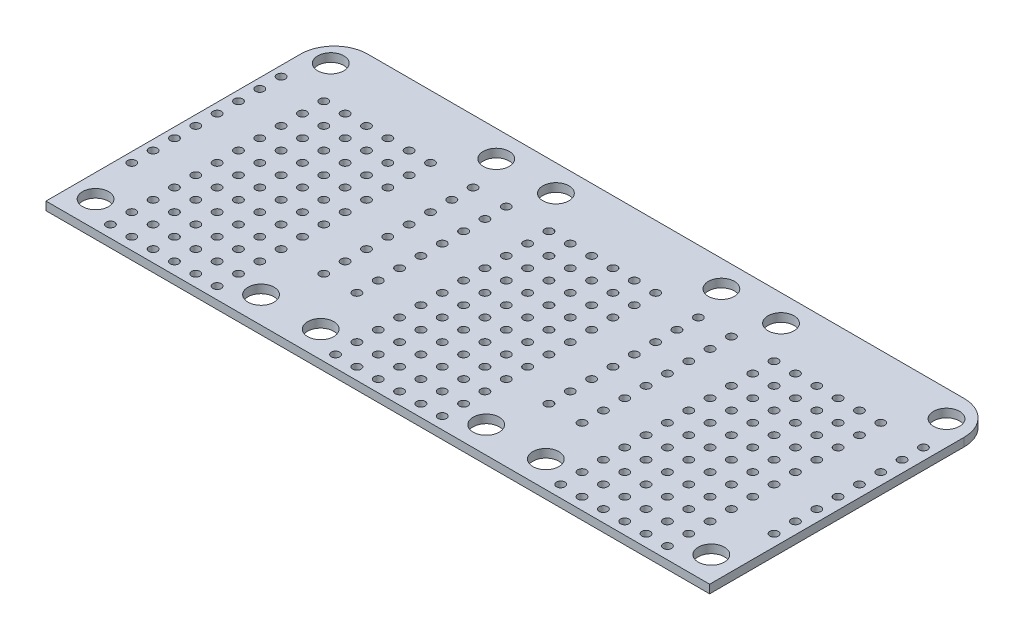
SolidWorks part; units mm, degrees
ref_plane "Front Plane" through (0, 0, 0) normal (0, 0, 1) x (1, 0, 0)
ref_plane "Top Plane" through (0, 0, 0) normal (0, 1, 0) x (1, 0, 0)
ref_plane "Right Plane" through (0, 0, 0) normal (1, 0, 0) x (0, 0, -1)
sketch "board" plane through (0, 0, 0) normal (0, 1, 0) x (1, 0, 0)
  line L1 (0, 0) -> (79, 0)
  line L2 (0, 0) -> (0, 34.3)
  line L3 (0, 34.3) -> (79, 34.3)
  line L4 (79, 0) -> (79, 34.3)
  dimension "D1" = 79
  dimension "D2" = 34.3
sketch "holes" plane through (0, 0, 0) normal (0, 1, 0) x (1, 0, 0)
  line L0 (0, 26.82) -> (1.17, 26.82) construction
  line L5 (1.17, 26.82) -> (6.25, 26.82) construction
  line L6 (2.75, 3.15) -> (22.45, 3.15) construction
  line L7 (22.45, 3.15) -> (22.45, 31.15) construction
  line L8 (22.45, 31.15) -> (2.75, 31.15) construction
  line L9 (2.75, 31.15) -> (2.75, 3.15) construction
  line L10 (12.6, 0) -> (12.6, 3.15) construction
  line L11 (6.25, 26.82) -> (6.25, 24.28) construction
  line L12 (6.25, 26.82) -> (8.79, 26.82) construction
  line L13 (1.17, 26.82) -> (24.03, 26.82) construction
  line L14 (0, 0) -> (2.75, 0) construction
  line L15 (2.75, 0) -> (2.75, 3.15) construction
  line L16 (2.75, 0) -> (12.6, 0) construction
  line L17 (1.17, 26.82) -> (1.17, 24.28) construction
  line L18 (0, 0) -> (0, 26.82) construction
  circle A0 centre (2.75, 31.15) radius 1.55
  circle A1 centre (22.45, 31.15) radius 1.55
  circle A2 centre (22.45, 3.15) radius 1.55
  circle A3 centre (2.75, 3.15) radius 1.55
  circle A4 centre (1.17, 26.82) radius 0.5
  circle A5 centre (24.03, 26.82) radius 0.5
  circle A6 centre (6.25, 26.82) radius 0.5
  circle A12 centre (1.17, 24.28) radius 0.5
  circle A13 centre (24.03, 24.28) radius 0.5
  circle A14 centre (1.17, 21.74) radius 0.5
  circle A15 centre (24.03, 21.74) radius 0.5
  circle A16 centre (1.17, 19.2) radius 0.5
  circle A17 centre (24.03, 19.2) radius 0.5
  circle A18 centre (1.17, 16.66) radius 0.5
  circle A19 centre (24.03, 16.66) radius 0.5
  circle A20 centre (1.17, 14.12) radius 0.5
  circle A21 centre (24.03, 14.12) radius 0.5
  circle A22 centre (1.17, 11.58) radius 0.5
  circle A23 centre (24.03, 11.58) radius 0.5
  circle A24 centre (1.17, 9.04) radius 0.5
  circle A25 centre (24.03, 9.04) radius 0.5
  circle A26 centre (6.25, 24.28) radius 0.5
  circle A27 centre (6.25, 21.74) radius 0.5
  circle A28 centre (6.25, 19.2) radius 0.5
  circle A29 centre (6.25, 16.66) radius 0.5
  circle A30 centre (6.25, 14.12) radius 0.5
  circle A31 centre (6.25, 11.58) radius 0.5
  circle A32 centre (6.25, 9.04) radius 0.5
  circle A33 centre (6.25, 6.5) radius 0.5
  circle A34 centre (6.25, 3.96) radius 0.5
  circle A35 centre (6.25, 1.42) radius 0.5
  circle A36 centre (8.79, 24.28) radius 0.5
  circle A37 centre (8.79, 21.74) radius 0.5
  circle A38 centre (8.79, 19.2) radius 0.5
  circle A39 centre (8.79, 16.66) radius 0.5
  circle A40 centre (8.79, 14.12) radius 0.5
  circle A41 centre (8.79, 11.58) radius 0.5
  circle A42 centre (8.79, 9.04) radius 0.5
  circle A43 centre (8.79, 6.5) radius 0.5
  circle A44 centre (8.79, 3.96) radius 0.5
  circle A45 centre (8.79, 1.42) radius 0.5
  circle A46 centre (11.33, 24.28) radius 0.5
  circle A47 centre (11.33, 21.74) radius 0.5
  circle A48 centre (11.33, 19.2) radius 0.5
  circle A49 centre (11.33, 16.66) radius 0.5
  circle A50 centre (11.33, 14.12) radius 0.5
  circle A51 centre (11.33, 11.58) radius 0.5
  circle A52 centre (11.33, 9.04) radius 0.5
  circle A53 centre (11.33, 6.5) radius 0.5
  circle A54 centre (11.33, 3.96) radius 0.5
  circle A55 centre (11.33, 1.42) radius 0.5
  circle A56 centre (13.87, 24.28) radius 0.5
  circle A57 centre (13.87, 21.74) radius 0.5
  circle A58 centre (13.87, 19.2) radius 0.5
  circle A59 centre (13.87, 16.66) radius 0.5
  circle A60 centre (13.87, 14.12) radius 0.5
  circle A61 centre (13.87, 11.58) radius 0.5
  circle A62 centre (13.87, 9.04) radius 0.5
  circle A63 centre (13.87, 6.5) radius 0.5
  circle A64 centre (13.87, 3.96) radius 0.5
  circle A65 centre (13.87, 1.42) radius 0.5
  circle A66 centre (16.41, 24.28) radius 0.5
  circle A67 centre (16.41, 21.74) radius 0.5
  circle A68 centre (16.41, 19.2) radius 0.5
  circle A69 centre (16.41, 16.66) radius 0.5
  circle A70 centre (16.41, 14.12) radius 0.5
  circle A71 centre (16.41, 11.58) radius 0.5
  circle A72 centre (16.41, 9.04) radius 0.5
  circle A73 centre (16.41, 6.5) radius 0.5
  circle A74 centre (16.41, 3.96) radius 0.5
  circle A75 centre (16.41, 1.42) radius 0.5
  circle A76 centre (18.95, 24.28) radius 0.5
  circle A77 centre (18.95, 21.74) radius 0.5
  circle A78 centre (18.95, 19.2) radius 0.5
  circle A79 centre (18.95, 16.66) radius 0.5
  circle A80 centre (18.95, 14.12) radius 0.5
  circle A81 centre (18.95, 11.58) radius 0.5
  circle A82 centre (18.95, 9.04) radius 0.5
  circle A83 centre (18.95, 6.5) radius 0.5
  circle A84 centre (18.95, 3.96) radius 0.5
  circle A85 centre (18.95, 1.42) radius 0.5
  circle A86 centre (8.79, 26.82) radius 0.5
  circle A87 centre (11.33, 26.82) radius 0.5
  circle A88 centre (13.87, 26.82) radius 0.5
  circle A89 centre (16.41, 26.82) radius 0.5
  circle A90 centre (18.95, 26.82) radius 0.5
  dimension "D6" = 3.1
  dimension "D7" = 1
  dimension "D10" = 22.86
  dimension "D2" = 2.75
  dimension "D3" = 19.7
  dimension "D4" = 28
  dimension "D5" = 1.17
  dimension "D8" = 3.15
  dimension "D9" = 5.08
  dimension "D11" = 26.82
  dimension "D12" = 8
  dimension "D14" = 2.54
  dimension "D17" = 2.54
  dimension "D18" = 2.54
  dimension "D15" = 11
  dimension "D16" = 6
extrude "Boss-Extrude1" add sketch "board" along normal blind 1
extrude "Cut-Extrude1" cut sketch "holes" along normal through all
pattern_linear "LPattern1" count 3 spacing 26.8 along (1, 0, 0) of "Cut-Extrude1"
fillet "Fillet1" radius 4 2 edges at (79, 0.5, -34.3) (0, 0.5, -34.3)
ref_axis "Axis1" through (1.17, 1, -26.82) along (0, -1, 0)
ref_axis "Axis2" through (24.03, 1, -26.82) along (0, -1, 0)
ref_axis "Axis3" through (27.97, 1, -26.82) along (0, -1, 0)
ref_axis "Axis4" through (50.83, 1, -26.82) along (0, -1, 0)
ref_axis "Axis5" through (54.77, 1, -26.82) along (0, -1, 0)
ref_axis "Axis6" through (77.63, 1, -26.82) along (0, -1, 0)
ref_axis "Axis7" through (2.75, 1, -31.15) along (0, -1, 0)
ref_axis "Axis8" through (22.45, 1, -31.15) along (0, -1, 0)
ref_axis "Axis9" through (29.55, 1, -31.15) along (0, -1, 0)
ref_axis "Axis10" through (49.25, 1, -31.15) along (0, -1, 0)
ref_axis "Axis11" through (56.35, 1, -31.15) along (0, -1, 0)
ref_axis "Axis12" through (76.05, 1, -31.15) along (0, -1, 0)
ref_plane "Mid" through (39.5, 0, 0) normal (1, 0, 0) x (0, 0, -1)
